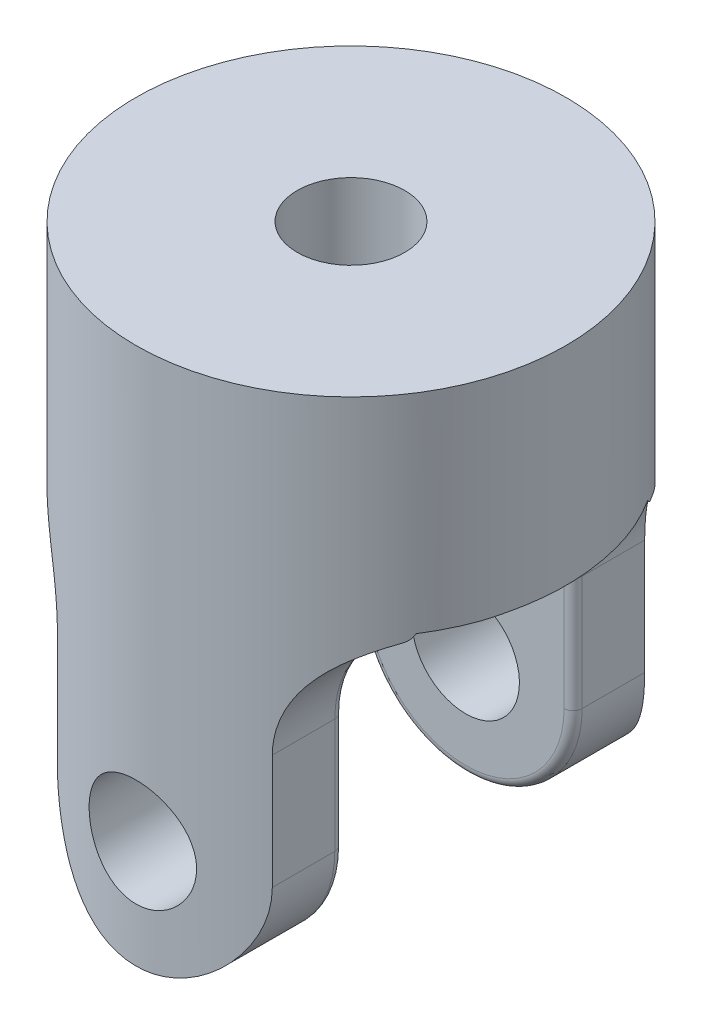
SolidWorks part; units mm, degrees
material "AISI 4340 Steel, normalized"
ref_plane "Front" through (0, 0, 0) normal (0, 0, 1) x (1, 0, 0)
ref_plane "Top" through (0, 0, 0) normal (0, 1, 0) x (-1, 0, 0)
ref_plane "Right" through (0, 0, 0) normal (1, 0, 0) x (0, 0, -1)
sketch "Sketch1" plane through (0, 0, 0) normal (0, 1, 0) x (-1, 0, 0)
  circle A0 centre (0, 0) radius 19.05
  dimension "D1" = 38.1
extrude "Base-Extrude" add sketch "Sketch1" along normal blind 47.625
sketch "Sketch2" plane through (0, 0, 0) normal (0, 0, 1) x (1, 0, 0)
  line L0 (0, 0) -> (0, 23.7435) construction
  line L1 (9.525, 9.525) -> (9.525, 19.685)
  line L2 (-9.525, 9.525) -> (-9.525, 19.685)
  line L3 (19.05, 29.21) -> (19.05, -1.3662)
  line L4 (19.05, -1.3662) -> (-19.05, -1.3662)
  line L5 (-19.05, -1.3662) -> (-19.05, 29.21)
  line L6 (19.05, 0) -> (-19.05, 0) construction
  arc A0 (-9.525, 9.525) -> (9.525, 9.525) centre (0, 9.525) ccw
  arc A1 (9.525, 19.685) -> (19.05, 29.21) centre (19.05, 19.685) cw
  arc A2 (-9.525, 19.685) -> (-19.05, 29.21) centre (-19.05, 19.685) ccw
  dimension "D3" = 9.525
  dimension "D1" = 38.1
  dimension "D2" = 19.05
  dimension "D4" = 29.21
extrude "Cut-Extrude1" cut sketch "Sketch2" against normal through all and the other way through all
sketch "Sketch8" plane through (0, 0, 0) normal (1, 0, 0) x (0, 0, -1)
  line L0 (-10.16, -7.4553) -> (10.16, -7.4553)
  line L1 (-10.16, -7.4553) -> (-10.16, 29.1452)
  line L2 (10.16, 29.1452) -> (-10.16, 29.1452)
  line L3 (10.16, 29.1452) -> (10.16, -7.4553)
  point P4 (0, 0)
  dimension "D1" = 10.16
  dimension "D2" = 20.32
extrude "Cut-Extrude5" cut sketch "Sketch8" against normal through all and the other way blind 47.625
fillet "Fillet1" radius 0.8001 10 edges at (11.3465, 25.287, -10.16) (9.525, 14.605, -10.16) (0, 0, -10.16) (-9.525, 14.605, -10.16) (-11.3465, 25.287, -10.16) (-11.3465, 25.287, 10.16) (-9.525, 14.605, 10.16) (0, 0, 10.16) (9.525, 14.605, 10.16) (11.3465, 25.287, 10.16)
sketch "Sketch11" plane through (0, 0, 0) normal (0, 0, 1) x (1, 0, 0)
  circle A0 centre (0, 9.525) radius 4.7625
  dimension "D1" = 9.525
extrude "Cut-Extrude6" cut sketch "Sketch11" against normal through all and the other way through all
sketch "Sketch12" plane through (0, 47.625, 0) normal (0, 1, 0) x (-1, 0, 0)
  circle A0 centre (0, 0) radius 4.7625
  dimension "D1" = 9.525
extrude "Cut-Extrude7" cut sketch "Sketch12" against normal through all
ref_axis "Axis1" through (0, 97.625, 0) along (0, -1, 0)
